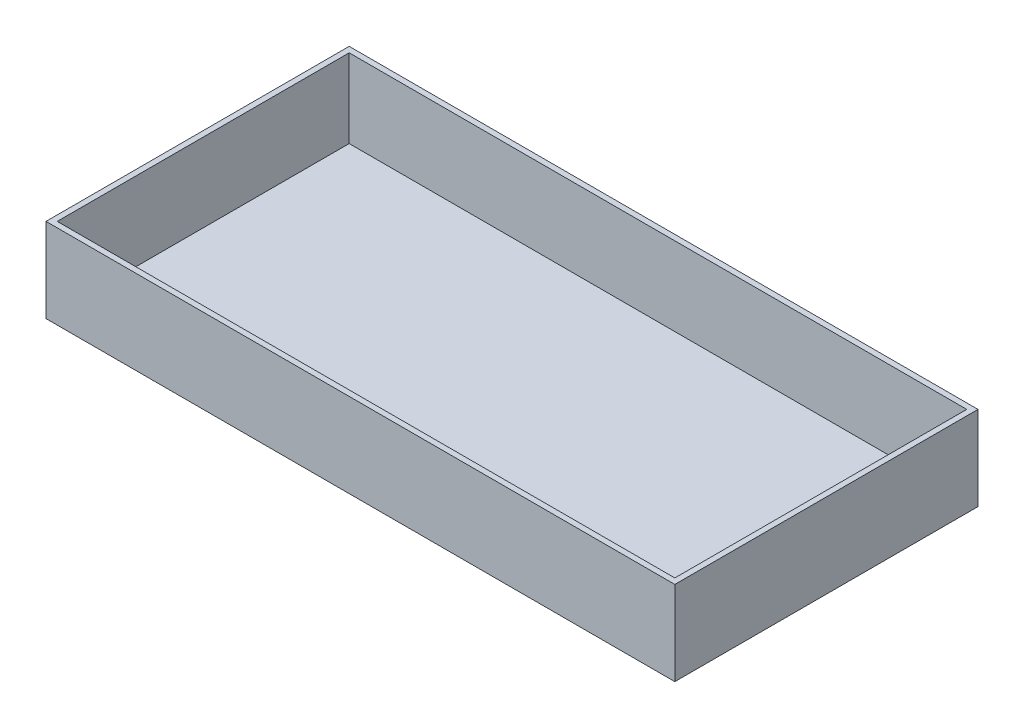
SolidWorks part; units mm, degrees
ref_plane "正面" through (0, 0, 0) normal (0, 0, 1) x (1, 0, 0)
ref_plane "平面" through (0, 0, 0) normal (0, 1, 0) x (1, 0, 0)
ref_plane "右側面" through (0, 0, 0) normal (1, 0, 0) x (0, 0, -1)
sketch "ｽｹｯﾁ1" plane through (0, 0, 0) normal (0, 1, 0) x (1, 0, 0)
  line L1 (-280, 135) -> (280, 135)
  line L2 (-280, 135) -> (-280, -135)
  line L3 (-280, -135) -> (280, -135)
  line L4 (280, 135) -> (280, -135)
  line L5 (-280, 135) -> (280, -135) construction
  line L6 (-280, -135) -> (280, 135) construction
  point P0 (0, 0)
  dimension "D1" = 270
  dimension "600" = 560
extrude "ﾎﾞｽ - 押し出し1" add sketch "ｽｹｯﾁ1" along normal blind 75
shell "ｼｪﾙ1" thickness 5 removed face at (0, 75, 0)
